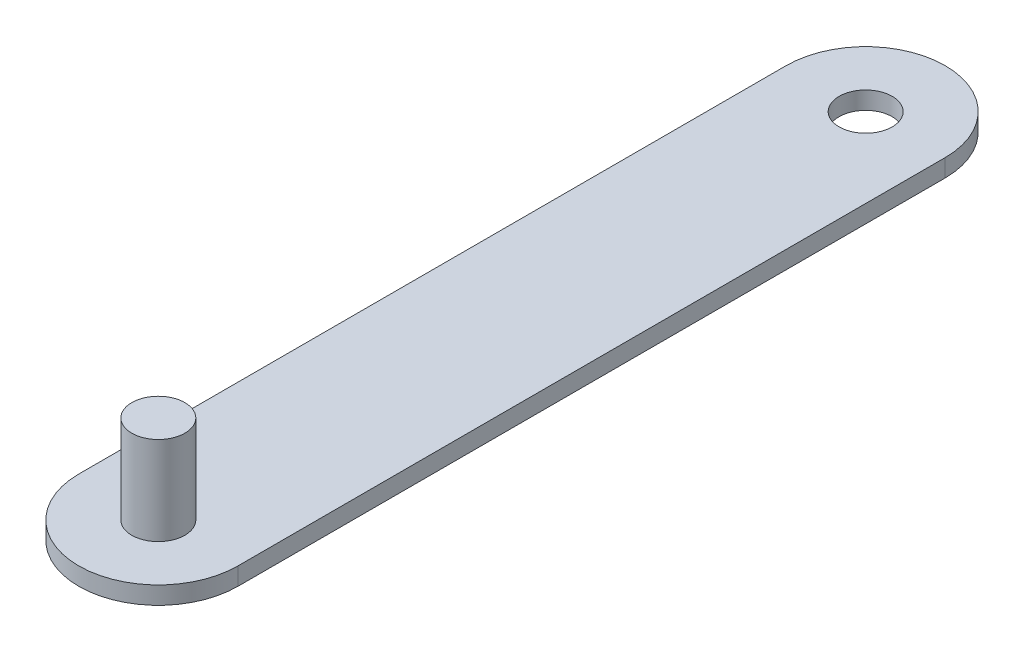
SolidWorks part; units mm, degrees
ref_plane "Front Plane" through (0, 0, 0) normal (0, 0, 1) x (1, 0, 0)
ref_plane "Top Plane" through (0, 0, 0) normal (0, 1, 0) x (1, 0, 0)
ref_plane "Right Plane" through (0, 0, 0) normal (1, 0, 0) x (0, 0, -1)
sketch "Sketch1" plane through (0, 0, 0) normal (0, 1, 0) x (1, 0, 0)
  line L1 (-225, -1000) -> (225, -1000)
  line L2 (-225, -1000) -> (-225, 1000)
  line L3 (-225, 1000) -> (225, 1000)
  line L4 (225, -1000) -> (225, 1000)
  line L5 (-225, -1000) -> (225, 1000) construction
  line L6 (-225, 1000) -> (225, -1000) construction
  arc A0 (225, -1000) -> (-225, -1000) centre (0, -1000) cw
  arc A1 (225, 1000) -> (-225, 1000) centre (0, 1000) ccw
  point P0 (0, 0)
  dimension "D1" = 2000
  dimension "D2" = 450
extrude "Boss-Extrude1" add sketch "Sketch1" along normal blind 50 contours L1 L4 L3 L2 | L3 A1 | A0 L1 region at (0, 0, 0) region at (0, 0, 1095.493) region at (0, 0, -1095.493)
sketch "Sketch2" plane through (0, 50, 0) normal (0, 1, 0) x (1, 0, 0)
  line L0 (-225, -1000) -> (225, -1000)
  line L1 (-225, -1000) -> (-225, 1000) construction
  circle A0 centre (0, -1000) radius 75
extrude "Boss-Extrude2" add sketch "Sketch2" along normal blind 250 contours L0 A0 | L0 A0 region at (0, 50, 968.169) region at (0, 50, 1031.831)
sketch "Sketch3" plane through (0, 50, 0) normal (0, 1, 0) x (1, 0, 0)
  line L0 (-225, 1000) -> (225, 1000)
  circle A0 centre (0, 1000) radius 75
extrude "Cut-Extrude2" cut sketch "Sketch3" against normal blind 250 contours L0 A0 | L0 A0 region at (0, 50, -1031.831) region at (0, 50, -968.169)
